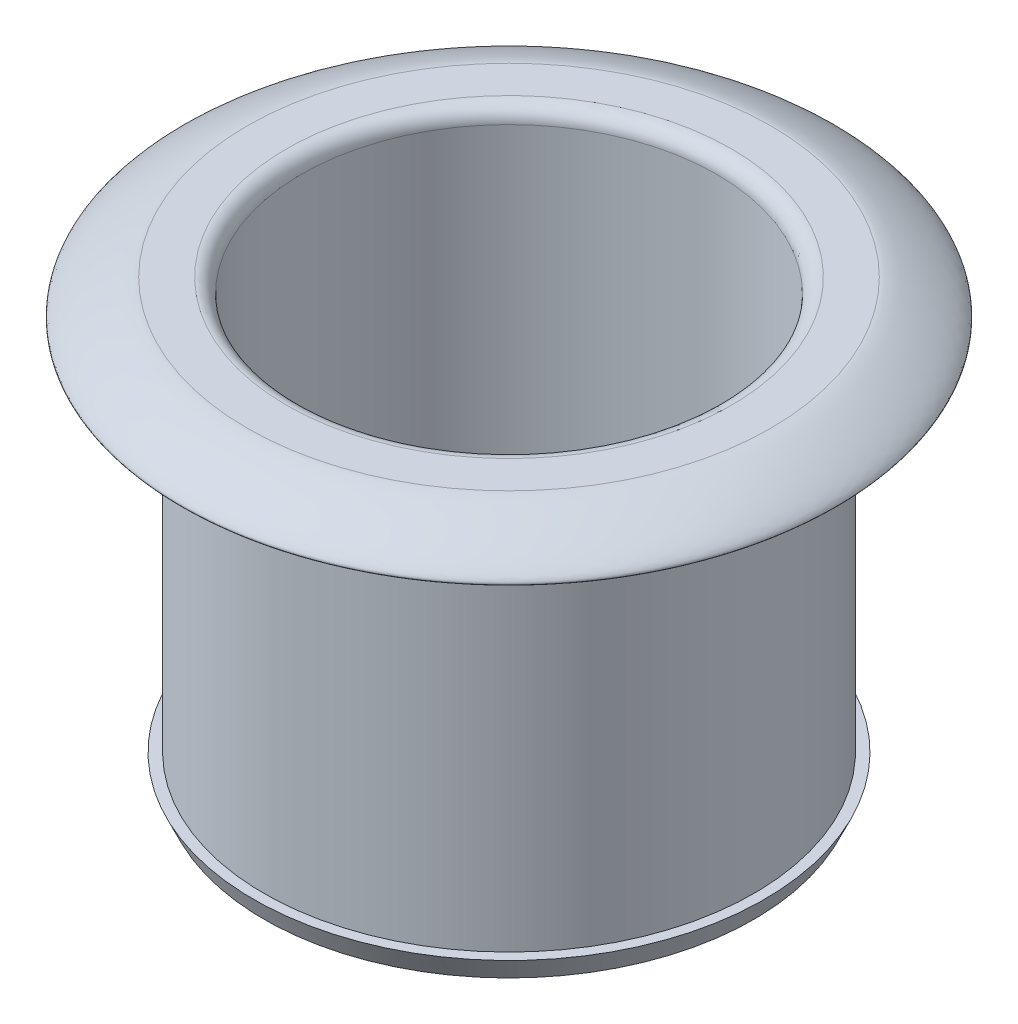
SolidWorks part; units mm, degrees
material "ABS"
ref_plane "Front Plane" through (0, 0, 0) normal (0, 0, 1) x (1, 0, 0)
ref_plane "Top Plane" through (0, 0, 0) normal (0, 1, 0) x (1, 0, 0)
ref_plane "Right Plane" through (0, 0, 0) normal (1, 0, 0) x (0, 0, -1)
sketch "Sketch1" plane through (0, 0, 0) normal (0, 0, 1) x (1, 0, 0)
  line L0 (0, 0) -> (14.097, 0) construction
  line L1 (14.097, 0) -> (16.637, 0)
  line L2 (16.637, 0) -> (16.637, 26.924)
  line L3 (16.637, 26.924) -> (21.717, 26.924)
  line L4 (14.097, 0) -> (14.097, 29.464)
  line L5 (14.097, 29.464) -> (17.7844, 29.464)
  line L6 (19.1269, 29.464) -> (16.4199, 29.464) construction
  line L7 (18.6537, 26.924) -> (21.9509, 26.924) construction
  line L8 (0, 0) -> (0, 29.464) construction
  line L9 (0, 29.464) -> (14.097, 29.464) construction
  line L10 (16.637, 1.524) -> (17.337, 1.524)
  line L11 (17.337, 1.524) -> (16.637, 0)
  spline S0 degree 3 poles (17.7844, 29.464) (18.9123, 29.464) (23.7777, 26.924) (21.717, 26.924) knots 0 0 0 0 1 1 1 1
  dimension "D1" = 16.637
  dimension "D2" = 2.54
  dimension "D3" = 2.54
  dimension "D4" = 26.924
  dimension "D5" = 5.08
  dimension "D6" = 25.4
  dimension "D7" = 0.7
revolve "Revolve1" add sketch "Sketch1" angle 360 about L8 region at (15.7916, 16.3391, 0) region at (16.8703, 1.016, 0)
fillet "Fillet1" radius 1 2 edges at (0, 0, -14.097) (0, 29.464, -14.097)
